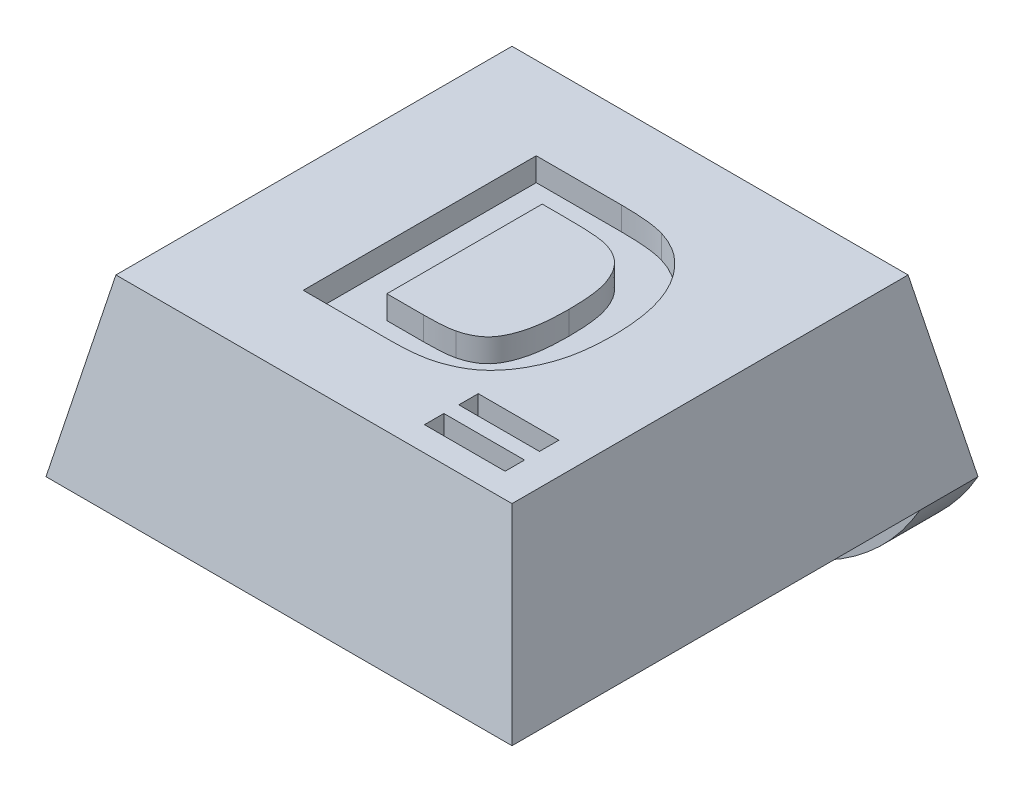
SolidWorks part; units mm, degrees
ref_plane "Front Plane" through (0, 0, 0) normal (0, 0, 1) x (1, 0, 0)
ref_plane "Top Plane" through (0, 0, 0) normal (0, 1, 0) x (1, 0, 0)
ref_plane "Right Plane" through (0, 0, 0) normal (1, 0, 0) x (0, 0, -1)
sketch "Sketch1" plane through (0, 0, 0) normal (0, 1, 0) x (1, 0, 0)
  line L1 (0, 0) -> (8, 0)
  line L2 (0, 0) -> (0, 8)
  line L3 (0, 8) -> (8, 8)
  line L4 (8, 0) -> (8, 8)
  dimension "D1" = 8
  dimension "D2" = 8
extrude "Boss-Extrude1" add sketch "Sketch1" along normal blind 3
sketch "Sketch2" plane through (0, 0, 0) normal (0, 0, 1) x (1, 0, 0)
  line L0 (0, 0) -> (0.6, 3)
  line L1 (0, 3) -> (8, 3) construction
  line L2 (0.6, 3) -> (0, 3)
  line L3 (0, 3) -> (0, 0)
  line L4 (8, 0) -> (7.4, 3)
  line L5 (7.4, 3) -> (8, 3)
  line L6 (8, 3) -> (8, 0)
  dimension "D1" = 0.6
  dimension "D2" = 0.6
extrude "Cut-Extrude1" cut sketch "Sketch2" against normal through all both and the other way through all
sketch "Sketch3" plane through (0, 0, 0) normal (1, 0, 0) x (0, 0, -1)
  line L0 (0, 0) -> (0.6, 3)
  line L1 (8, 3) -> (0, 3) construction
  line L2 (0.6, 3) -> (0, 3)
  line L3 (0, 3) -> (0, 0)
  line L4 (8, 3) -> (7.4, 3)
  line L5 (7.4, 3) -> (8, 0)
  line L6 (8, 3) -> (8, 0)
  dimension "D1" = 0.6
  dimension "D2" = 0.6
extrude "Cut-Extrude2" cut sketch "Sketch3" along normal blind 11
sketch "Sketch4" plane through (0, 0, 0) normal (0, -1, 0) x (1, 0, 0)
  line L0 (8, 0) -> (8, -8) construction
  line L3 (0, 0) -> (8, 0) construction
  circle A0 centre (4, -3.75) radius 1.75
  dimension "D1" = 3.5
  dimension "D2" = 4
  dimension "D3" = 3.75
extrude "Cut-Extrude3" cut sketch "Sketch4" against normal blind 0.4
sketch "Sketch5" plane through (0, 0, 0) normal (0, -1, 0) x (1, 0, 0)
  line L0 (8, 0) -> (8, -8) construction
  line L1 (0, -8) -> (8, -8)
  line L2 (0, -8) -> (0, -7)
  line L3 (0, -7) -> (8, -7)
  line L4 (8, -8) -> (8, -7)
  dimension "D1" = 1
extrude "Boss-Extrude2" add sketch "Sketch5" along normal blind 2
fillet "Fillet1" radius 4 2 edges at (8, -2, -7.5) (0, -2, -7.5)
sketch "Sketch6" plane through (0, 3, 0) normal (0, 1, 0) x (1, 0, 0)
  text T0 "D" font "Arial" height 4
extrude "Cut-Extrude4" cut sketch "Sketch6" against normal blind 0.4
sketch "Sketch7" plane through (0, 3, 0) normal (0, 1, 0) x (1, 0, 0)
  text T0 "=" font "Arial" height 2
extrude "Cut-Extrude5" cut sketch "Sketch7" against normal blind 0.55
